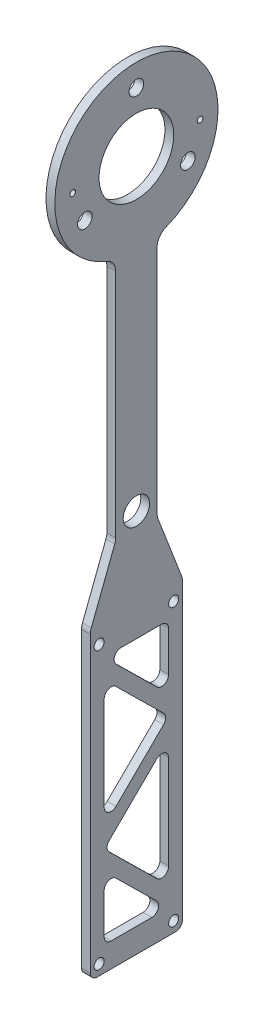
SolidWorks part; units mm, degrees
material "1060 Alloy"
ref_plane "Front Plane" through (0, 0, 0) normal (0, 0, 1) x (1, 0, 0)
ref_plane "Top Plane" through (0, 0, 0) normal (0, 1, 0) x (1, 0, 0)
ref_plane "Right Plane" through (0, 0, 0) normal (1, 0, 0) x (0, 0, -1)
sketch "Sketch1" plane through (0, 0, 0) normal (1, 0, 0) x (0, 0, -1)
  line L0 (-13.4747, 0) -> (13.4747, 0) construction
  line L1 (0, 0) -> (0, 35) construction
  line L2 (-13.4747, 0) -> (0, 35) construction
  line L3 (0, 35) -> (13.4747, 0) construction
  line L4 (13.4747, 0) -> (-13.4747, 0) construction
  line L5 (20.7574, -5) -> (-20.7574, -5)
  line L6 (-20.7574, -5) -> (0, 48.9165)
  line L7 (0, 48.9165) -> (20.7574, -5)
  line L8 (0, 35) -> (0, 146) construction
  line L9 (0, 35) -> (0, 146) construction
  line L12 (-7.5, 35) -> (-7.5, 146)
  line L13 (7.5, 35) -> (7.5, 146)
  line L14 (-7.5, 35) -> (-7.5, 29.4356)
  line L15 (7.5, 35) -> (7.5, 29.4356)
  line L16 (-13.4747, 0) -> (13.4747, 0) construction
  line L17 (-13.4747, 0) -> (-13.4747, -100) construction
  line L18 (13.4747, 0) -> (13.4747, -100) construction
  line L19 (-13.4747, -100) -> (13.4747, -100) construction
  line L20 (-20.7574, -5) -> (20.7574, -5)
  line L21 (-20.7574, -5) -> (-20.7574, -103.81)
  line L22 (20.7574, -5) -> (20.7574, -103.81)
  line L23 (-20.7574, -103.81) -> (20.7574, -103.81)
  circle A0 centre (-13.4747, 0) radius 1.8288
  circle A1 centre (0, 35) radius 4.7625
  circle A2 centre (13.4747, 0) radius 1.8288
  circle A3 centre (0, 146) radius 3 construction
  arc A6 (-7.5, 35) -> (7.5, 35) centre (0, 35) ccw
  arc A7 (7.5, 146) -> (-7.5, 146) centre (0, 146) ccw
  circle A8 centre (-13.4747, -100) radius 1.8288
  circle A9 centre (13.4747, -100) radius 1.8288
  circle A10 centre (0, 146) radius 21.5 construction
  circle A11 centre (0, 167.5) radius 2.65
  circle A12 centre (-18.6195, 135.25) radius 2.65
  circle A13 centre (18.6195, 135.25) radius 2.65
  arc A14 (0, 167.5) -> (-18.6195, 135.25) centre (0, 146) ccw construction
  arc A15 (0, 167.5) -> (18.6195, 135.25) centre (0, 146) cw construction
  arc A16 (-18.6195, 135.25) -> (18.6195, 135.25) centre (0, 146) ccw construction
  circle A17 centre (0, 146) radius 13.5
  circle A18 centre (0, 146) radius 29.5
  point P4 (0, 0)
  point P14 (0, 90.5)
  point P34 (0, 146)
  dimension "D3" = 3.6576
  dimension "D4" = 9.525
  dimension "D7" = 6
  dimension "D11" = 43
  dimension "D12" = 5.3
  dimension "D13" = 27
  dimension "D14" = 59
  dimension "D1" = 26.9494
  dimension "D5" = 111
  dimension "D6" = 15
  dimension "D8" = 100
  dimension "D9" = 3.81
  dimension "D10" = 35
  dimension "D2" = 5
extrude "Boss-Extrude1" add sketch "Sketch1" along normal blind 3.175 contours L13 A18 L12 A17 A11 A12 A13 | L12 A18 L13 A17 | A18 L12 A6 L6 L7 L13 | L6 A6 L7 A1 | A6 L6 L5 L7 A2 A0 | A6 L14 L6 | A6 L7 L15 | L21 L23 L22 L5 A9 A8 region at (0, -54.1702, 0) region at (0, 9.5725, 0) region at (0, 31.6598, -7.2402) region at (0, 31.6598, 7.2402) region at (0, 27.7524, 0) region at (0, 77.9388, 0) region at (0, 125.037, 0) region at (0, 126.1222, -8.3276)
sketch "Sketch2" plane through (3.175, 0, 0) normal (1, 0, 0) x (0, 0, -1)
  line L0 (-11.645, -5) -> (11.645, -5) construction
  line L1 (-11.645, -95) -> (11.645, -95) construction
  line L2 (11.645, -95) -> (11.645, -5) construction
  line L3 (-11.645, -95) -> (-11.645, -5) construction
  line L6 (11.645, -38.5118) -> (-11.645, -61.4882) construction
  line L7 (11.645, -5) -> (-11.645, -5)
  line L8 (-11.645, -5) -> (11.645, -27.9764)
  line L9 (11.645, -27.9764) -> (11.645, -5)
  line L10 (-11.645, -12.0236) -> (11.645, -35)
  line L11 (11.645, -35) -> (-11.645, -57.9764)
  line L12 (-11.645, -57.9764) -> (-11.645, -35)
  line L13 (-11.645, -35) -> (-11.645, -12.0236)
  line L14 (-11.645, -72.0236) -> (-11.645, -95)
  line L15 (-11.645, -95) -> (11.645, -95)
  line L16 (11.645, -95) -> (-11.645, -72.0236)
  line L17 (11.645, -42.0236) -> (11.645, -65)
  line L18 (11.645, -65) -> (11.645, -87.9764)
  line L19 (11.645, -87.9764) -> (-11.645, -65)
  line L20 (-11.645, -65) -> (11.645, -42.0236)
  line L21 (16.645, -1056.0877) -> (16.645, 48943.9123) construction
  line L22 (-16.645, -1060.2922) -> (-16.645, 48939.7078) construction
  line L23 (16.645, 29.4356) -> (-16.645, 29.4356) construction
  line L24 (-20.7574, -103.81) -> (-16.645, -103.81)
  line L25 (-20.7574, -103.81) -> (-20.7574, 29.4356)
  line L26 (-16.645, -103.81) -> (-16.645, 29.4356)
  line L27 (-20.7574, 29.4356) -> (-16.645, 29.4356)
  line L28 (-20.7574, -103.81) -> (20.7574, -103.81) construction
  line L29 (20.7574, -103.81) -> (16.645, -103.81)
  line L30 (20.7574, -103.81) -> (20.7574, 29.4356)
  line L31 (16.645, -103.81) -> (16.645, 29.4356)
  line L32 (20.7574, 29.4356) -> (16.645, 29.4356)
  circle A0 centre (13.4747, 0) radius 1.8288 construction
  circle A1 centre (13.4747, -100) radius 1.8288 construction
  point P6 (11.645, -50)
  point P10 (0, 29.4356)
  point P21 (0, -50)
  dimension "D1" = 33.29
  dimension "D2" = 5
  dimension "D3" = 5
  dimension "D4" = 5
  dimension "D5" = 5
  dimension "D6" = 2.5
  dimension "D8" = 5
  dimension "D7" = 2
extrude "Cut-Extrude1" cut sketch "Sketch2" against normal up to next
fillet "Fillet3" radius 2.5 14 edges at (1.5875, -57.9764, 11.645) (1.5875, -35, -11.645) (1.5875, -95, -11.645) (1.5875, -72.0236, 11.645) (1.5875, -95, 11.645) (1.5875, -27.9764, -11.645) (1.5875, -5, -11.645) (1.5875, -12.0236, 11.645) (1.5875, -5, 11.645) (1.5875, -87.9764, -11.645) (1.5875, -42.0236, -11.645) (1.5875, -65, 11.645) (1.5875, -103.81, -16.645) (1.5875, -103.81, 16.645)
fillet "Fillet4" radius 5 6 edges at (1.5875, 29.4356, -7.5) (1.5875, 29.4356, 7.5) (1.5875, 5.6818, 16.645) (1.5875, 5.6818, -16.645) (1.5875, 117.4693, -7.5) (1.5875, 117.4693, 7.5)
hole_wizard "M2.5x0.45 Tapped Hole1" positions "Sketch3" profile "Sketch4" tap size "M2.5x0.45" standard "ANSI Metric" end condition up to next
sketch "Sketch3" plane through (3.175, 0, 0) normal (1, 0, 0) x (0, 0, -1)
  line L0 (0, 167.5) -> (0, 146) construction
  line L2 (0, 146) -> (50000, 146) construction
  circle A0 centre (0, 146) radius 23.015 construction
  point P15 (-23.015, 146)
  point P17 (23.015, 146)
  dimension "D1" = 46.03
sketch "Sketch4" plane through (3.175, 146, -23.015) normal (0, 1, 0) x (0, 0, -1)
  line L0 (0, 0) -> (0, 3.175)
  line L1 (0, 3.175) -> (1.025, 3.175)
  line L2 (1.025, 3.175) -> (1.025, 0)
  line L5 (1.025, 0) -> (0, 0)
  line L11 (0, -6.35) -> (0, 107.95) construction
  dimension "Thru Tap Drill Dia." = 2.05
  dimension "Thru Tap Drill Depth" = 3.175
cosmetic thread "Hole Thread1" parameters "D2"=2.5
cosmetic thread "Hole Thread2" parameters "D2"=2.5
